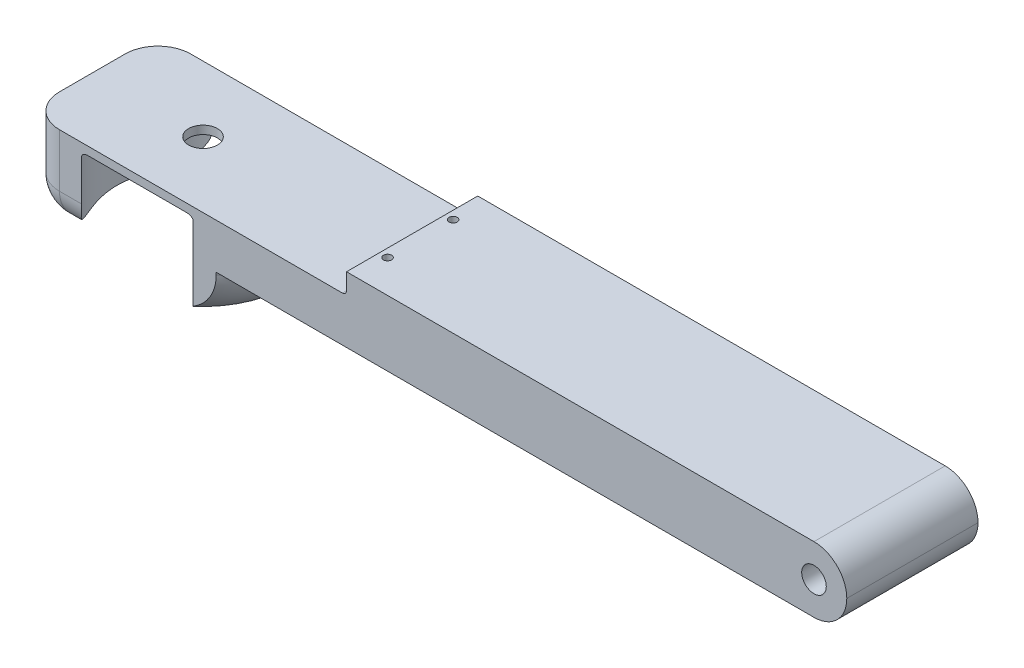
SolidWorks part; units mm, degrees
ref_plane "Front Plane" through (0, 0, 0) normal (0, 0, 1) x (1, 0, 0)
ref_plane "Top Plane" through (0, 0, 0) normal (0, 1, 0) x (1, 0, 0)
ref_plane "Right Plane" through (0, 0, 0) normal (1, 0, 0) x (0, 0, -1)
sketch "Sketch1" plane through (0, 0, 0) normal (0, 1, 0) x (1, 0, 0)
  line L1 (-5, 8) -> (5, 8)
  line L2 (-5, 8) -> (-5, -8)
  line L3 (-5, -8) -> (5, -8)
  line L4 (5, 8) -> (5, -8)
  line L5 (-5, 8) -> (5, -8) construction
  line L6 (-5, -8) -> (5, 8) construction
  point P0 (0, 0)
  dimension "D1" = 16
  dimension "D2" = 10
extrude "Boss-Extrude1" add sketch "Sketch1" along normal blind 8
fillet "Fillet1" radius 4 2 edges at (5, 0, 0) (5, 8, 0)
sketch "Sketch2" plane through (0, 0, 8) normal (0, 0, 1) x (1, 0, 0)
  line L0 (1, 8) -> (1, 0) construction
  arc A0 (1, 0) -> (5, 4) centre (1, 4) ccw construction
  circle A1 centre (1, 4) radius 1.5
  dimension "D1" = 3
extrude "Cut-Extrude1" cut sketch "Sketch2" against normal blind 16
sketch "Sketch3" plane through (0, 0, 0) normal (0, 1, 0) x (1, 0, 0)
  line L0 (-5, 8) -> (-5, -8)
  line L1 (-5, 8) -> (-56, 8)
  line L2 (-5, -8) -> (-56, -8)
  line L3 (-56, 8) -> (-56, -8)
  dimension "D1" = 51
extrude "Boss-Extrude2" add sketch "Sketch3" along normal blind 8
sketch "Sketch4" plane through (0, 0, 0) normal (0, 1, 0) x (1, 0, 0)
  line L0 (-56, 8) -> (-56, -8)
  line L1 (-56, 8) -> (-92, 8)
  line L2 (-56, -8) -> (-92, -8)
  line L3 (-92, 8) -> (-92, -8)
  dimension "D1" = 36
extrude "Boss-Extrude3" add sketch "Sketch4" along normal blind 4.5
sketch "Sketch6" plane through (0, 4.5, 0) normal (0, 1, 0) x (1, 0, 0)
  line L0 (-92, 0) -> (-81.5, 0) construction
  line L1 (-92, 8) -> (-92, -8) construction
  circle A0 centre (-81.5, 0) radius 10.5
  dimension "D1" = 10.5
extrude "Cut-Extrude6" cut sketch "Sketch6" against normal blind 16
sketch "Sketch11" plane through (0, 0, 0) normal (0, 1, 0) x (1, 0, 0)
  line L0 (-92, 8) -> (-92, -8)
  line L1 (-92, 8) -> (-95, 8)
  line L2 (-92, -8) -> (-95, -8)
  line L3 (-95, 8) -> (-95, -8)
  dimension "D1" = 3
extrude "Boss-Extrude4" add sketch "Sketch11" along normal blind 4.5
fillet "Fillet3" radius 4 2 edges at (-95, 2.25, 8) (-95, 2.25, -8)
sketch "Sketch13" plane through (0, 4.5, 0) normal (0, 1, 0) x (1, 0, 0)
  line L0 (-88.3007, 8) -> (-91, 8) construction
  line L1 (-95, 4) -> (-95, -4) construction
  line L2 (-91, -8) -> (-88.3007, -8) construction
  line L3 (-74.6993, -8) -> (-56, -8) construction
  line L4 (-56, 8) -> (-74.6993, 8) construction
  line L5 (-56, -8) -> (-56, 8) construction
  line L6 (-88.3007, 8) -> (-91, 8)
  line L7 (-95, 4) -> (-95, -4)
  line L8 (-91, -8) -> (-88.3007, -8)
  line L9 (-74.6993, -8) -> (-56, -8)
  line L10 (-56, 8) -> (-74.6993, 8)
  line L11 (-56, -8) -> (-56, 8)
  line L12 (-88.3007, 8) -> (-74.6993, 8)
  line L13 (-74.6993, -8) -> (-88.3007, -8)
  arc A0 (-91, 8) -> (-95, 4) centre (-91, 4) ccw construction
  arc A1 (-95, -4) -> (-91, -8) centre (-91, -4) ccw construction
  arc A2 (-91, 8) -> (-95, 4) centre (-91, 4) ccw
  arc A3 (-95, -4) -> (-91, -8) centre (-91, -4) ccw
extrude "Boss-Extrude5" add sketch "Sketch13" along normal blind 1
sketch "Sketch14" plane through (0, 5.5, 0) normal (0, 1, 0) x (1, 0, 0)
  circle A0 centre (-81.5, 0) radius 1.75
  dimension "D1" = 3.5
extrude "Cut-Extrude7" cut sketch "Sketch14" against normal blind 1
sketch "Sketch15" plane through (0, 0, 0) normal (0, -1, 0) x (1, 0, 0)
  line L0 (-91, 8) -> (-88.3007, 8) construction
  line L1 (-95, -4) -> (-95, 4) construction
  line L2 (-88.3007, -8) -> (-91, -8) construction
  line L3 (-91, 8) -> (-88.3007, 8)
  line L4 (-95, -4) -> (-95, 4)
  line L5 (-88.3007, -8) -> (-91, -8)
  line L9 (1, 8) -> (-74.6993, 8) construction
  line L10 (-74.6993, -8) -> (1, -8) construction
  line L15 (-71.8953, 8) -> (-74.6993, 8)
  line L16 (-74.6993, -8) -> (-71.8953, -8)
  arc A0 (-91, 8) -> (-95, 4) centre (-91, 4) ccw construction
  arc A1 (-95, -4) -> (-91, -8) centre (-91, -4) ccw construction
  arc A2 (-91, 8) -> (-95, 4) centre (-91, 4) ccw
  arc A3 (-95, -4) -> (-91, -8) centre (-91, -4) ccw
  arc A5 (-74.6993, -8) -> (-74.6993, 8) centre (-81.5, 0) ccw construction
  arc A7 (-88.3007, 8) -> (-88.3007, -8) centre (-81.5, 0) ccw construction
  arc A8 (-88.3007, 8) -> (-88.3007, -8) centre (-81.5, 0) ccw
  arc A9 (-74.6993, -8) -> (-74.6993, 8) centre (-81.5, 0) ccw
  arc A10 (-71.8953, -8) -> (-71.8953, 8) centre (-81.5, 0) ccw
extrude "Boss-Extrude6" add sketch "Sketch15" along normal blind 5
fillet "Fillet4" radius 6.5 1 edges at (-69, -5, 0)
fillet "Fillet5" radius 0.5 2 edges at (-71, 4.5, 0) (-92, 4.5, 0)
fillet "Fillet6" radius 4 5 edges at (-89.6504, -5, 8) (-93.8284, -5, 6.8284) (-89.6504, -5, -8) (-93.8284, -5, -6.8284) (-95, -5, 0)
fillet "Fillet7" radius 0.5 1 edges at (-56, 5.5, 0)
sketch "Sketch16" plane through (0, 8, 0) normal (0, 1, 0) x (1, 0, 0)
  line L0 (-56, 0) -> (-54, 0) construction
  line L1 (-56, 8) -> (-56, -8) construction
  line L2 (-54, 0) -> (-56, 8) construction
  line L3 (-54, 0) -> (-56, -8) construction
  line L4 (-54, 8) -> (-54, -8) construction
  line L5 (1, 8) -> (-56, 8) construction
  line L6 (-56, -8) -> (1, -8) construction
  line L7 (-54, -8) -> (-54, -6.1) construction
  line L8 (-54, 8) -> (-54, 6.1) construction
  line L9 (1, 0) -> (-3, 0) construction
  line L10 (1, -8) -> (1, 8) construction
  line L11 (-54, 6.1) -> (-54, -6.1)
  line L12 (-54, 6.1) -> (-3, 6.1)
  line L13 (-54, -6.1) -> (-3, -6.1)
  line L14 (-3, 6.1) -> (-3, -6.1)
  circle A0 centre (-55, 4) radius 0.5 construction
  circle A1 centre (-55, -4) radius 0.5 construction
  dimension "D2" = 1
  dimension "D3" = 1
  dimension "D4" = 1.9
  dimension "D1" = 2
  dimension "D5" = 1.9
  dimension "D6" = 4
  dimension "D7" = 12.2
  dimension "D8" = 51
sketch "Sketch17" plane through (0, 0, 0) normal (0, -1, 0) x (1, 0, 0)
  line L1 (-54, 6.1) -> (-3, 6.1) construction
  line L11 (-54, -6.1) -> (-54, 6.1) construction
  line L12 (-54, -6.1) -> (-3, -6.1) construction
  line L13 (-3, -6.1) -> (-3, 6.1) construction
  line L14 (-54, 6.1) -> (-3, 6.1)
  line L15 (-54, -6.1) -> (-54, 6.1)
  line L16 (-54, -6.1) -> (-3, -6.1)
  line L17 (-3, -6.1) -> (-3, 6.1)
extrude "Cut-Extrude9" cut sketch "Sketch17" against normal blind 6
sketch "Sketch18" plane through (0, 0, 0) normal (0, -1, 0) x (1, 0, 0)
  circle A0 centre (-55, 4) radius 0.5 construction
  circle A1 centre (-55, -4) radius 0.5 construction
  circle A2 centre (-55, 4) radius 0.5
  circle A3 centre (-55, -4) radius 0.5
extrude "Cut-Extrude10" cut sketch "Sketch18" against normal blind 8
